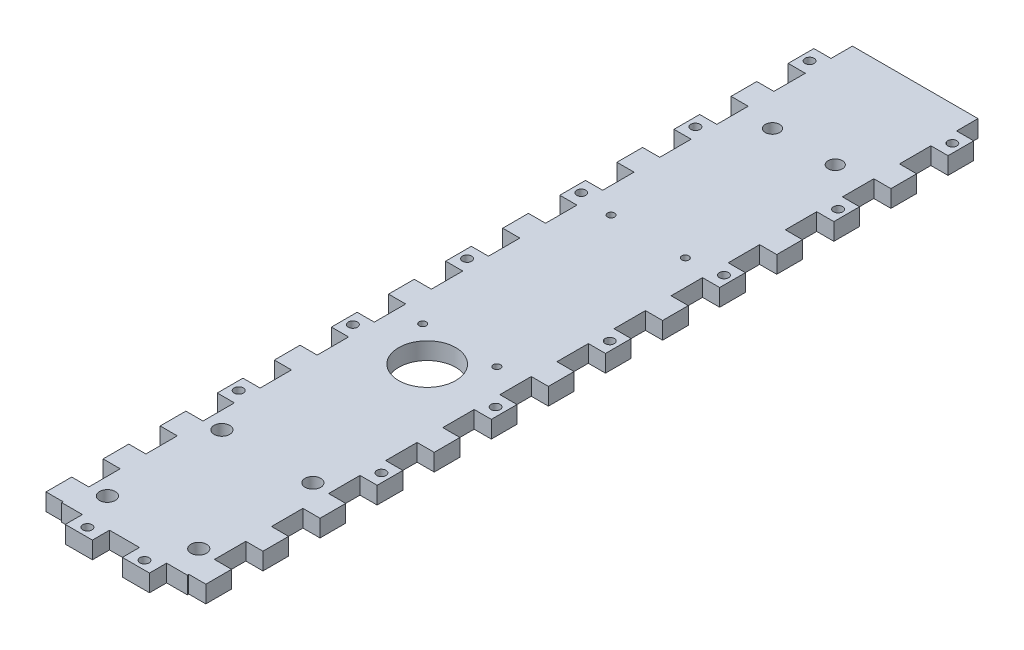
SolidWorks part; units mm, degrees
ref_plane "Plan de face" through (0, 0, 0) normal (0, 0, 1) x (1, 0, 0)
ref_plane "Plan de dessus" through (0, 0, 0) normal (0, 1, 0) x (1, 0, 0)
ref_plane "Plan de droite" through (0, 0, 0) normal (1, 0, 0) x (0, 0, -1)
sketch "Sketch1" plane through (0, 0, 0) normal (0, 0, 1) x (1, 0, 0)
  line L1 (-30.0201, 10.5217) -> (13.9799, 10.5217)
  line L2 (-30.0201, 10.5217) -> (-30.0201, 4.5217)
  line L3 (-30.0201, 4.5217) -> (13.9799, 4.5217)
  line L4 (13.9799, 10.5217) -> (13.9799, 4.5217)
  dimension "D1" = 44
  dimension "D2" = 6
extrude "Boss-Extrude1" add sketch "Sketch1" along normal blind 277
sketch "Sketch4" plane through (13.9799, 0, 0) normal (1, 0, 0) x (0, 0, -1)
  line L0 (-277, 10.5217) -> (0, 10.5217) construction
  line L1 (-276.5, 10.5217) -> (-267.5, 10.5217)
  line L2 (-276.5, 10.5217) -> (-276.5, 4.5217)
  line L3 (-276.5, 4.5217) -> (-267.5, 4.5217)
  line L4 (-267.5, 10.5217) -> (-267.5, 4.5217)
  line L5 (-277, 4.5217) -> (0, 4.5217) construction
  line L6 (-277, 4.5217) -> (-277, 10.5217) construction
  line L7 (-256.5, 10.5217) -> (-256.5, 4.5217)
  line L8 (-256.5, 10.5217) -> (-247.5, 10.5217)
  line L9 (-247.5, 10.5217) -> (-247.5, 4.5217)
  line L10 (-256.5, 4.5217) -> (-247.5, 4.5217)
  line L11 (-236.5, 10.5217) -> (-236.5, 4.5217)
  line L12 (-236.5, 10.5217) -> (-227.5, 10.5217)
  line L13 (-227.5, 10.5217) -> (-227.5, 4.5217)
  line L14 (-236.5, 4.5217) -> (-227.5, 4.5217)
  line L15 (-216.5, 10.5217) -> (-216.5, 4.5217)
  line L16 (-216.5, 10.5217) -> (-207.5, 10.5217)
  line L17 (-207.5, 10.5217) -> (-207.5, 4.5217)
  line L18 (-216.5, 4.5217) -> (-207.5, 4.5217)
  line L19 (-196.5, 10.5217) -> (-196.5, 4.5217)
  line L20 (-196.5, 10.5217) -> (-187.5, 10.5217)
  line L21 (-187.5, 10.5217) -> (-187.5, 4.5217)
  line L22 (-196.5, 4.5217) -> (-187.5, 4.5217)
  line L23 (-176.5, 10.5217) -> (-176.5, 4.5217)
  line L24 (-176.5, 10.5217) -> (-167.5, 10.5217)
  line L25 (-167.5, 10.5217) -> (-167.5, 4.5217)
  line L26 (-176.5, 4.5217) -> (-167.5, 4.5217)
  line L27 (-156.5, 10.5217) -> (-156.5, 4.5217)
  line L28 (-156.5, 10.5217) -> (-147.5, 10.5217)
  line L29 (-147.5, 10.5217) -> (-147.5, 4.5217)
  line L30 (-156.5, 4.5217) -> (-147.5, 4.5217)
  line L31 (-136.5, 10.5217) -> (-136.5, 4.5217)
  line L32 (-136.5, 10.5217) -> (-127.5, 10.5217)
  line L33 (-127.5, 10.5217) -> (-127.5, 4.5217)
  line L34 (-136.5, 4.5217) -> (-127.5, 4.5217)
  line L35 (-116.5, 10.5217) -> (-116.5, 4.5217)
  line L36 (-116.5, 10.5217) -> (-107.5, 10.5217)
  line L37 (-107.5, 10.5217) -> (-107.5, 4.5217)
  line L38 (-116.5, 4.5217) -> (-107.5, 4.5217)
  line L39 (-96.5, 10.5217) -> (-96.5, 4.5217)
  line L40 (-96.5, 10.5217) -> (-87.5, 10.5217)
  line L41 (-87.5, 10.5217) -> (-87.5, 4.5217)
  line L42 (-96.5, 4.5217) -> (-87.5, 4.5217)
  line L43 (-76.5, 10.5217) -> (-76.5, 4.5217)
  line L44 (-76.5, 10.5217) -> (-67.5, 10.5217)
  line L45 (-67.5, 10.5217) -> (-67.5, 4.5217)
  line L46 (-76.5, 4.5217) -> (-67.5, 4.5217)
  line L47 (-56.5, 10.5217) -> (-56.5, 4.5217)
  line L48 (-56.5, 10.5217) -> (-47.5, 10.5217)
  line L49 (-47.5, 10.5217) -> (-47.5, 4.5217)
  line L50 (-56.5, 4.5217) -> (-47.5, 4.5217)
  line L51 (-36.5, 10.5217) -> (-36.5, 4.5217)
  line L52 (-36.5, 10.5217) -> (-27.5, 10.5217)
  line L53 (-27.5, 10.5217) -> (-27.5, 4.5217)
  line L54 (-36.5, 4.5217) -> (-27.5, 4.5217)
  line L55 (-16.5, 10.5217) -> (-16.5, 4.5217)
  line L56 (-16.5, 10.5217) -> (-7.5, 10.5217)
  line L57 (-7.5, 10.5217) -> (-7.5, 4.5217)
  line L58 (-16.5, 4.5217) -> (-7.5, 4.5217)
  dimension "D1" = 0.5
  dimension "D2" = 9
  dimension "D3" = 14
extrude "Boss-Extrude2" add sketch "Sketch4" along normal blind 6
sketch "Sketch5" plane through (-30.0201, 0, 0) normal (-1, 0, 0) x (0, 0, 1)
  line L0 (277, 4.5217) -> (0, 4.5217) construction
  line L1 (276.5, 4.5217) -> (267.5, 4.5217)
  line L2 (276.5, 4.5217) -> (276.5, 10.5217)
  line L3 (276.5, 10.5217) -> (267.5, 10.5217)
  line L4 (267.5, 4.5217) -> (267.5, 10.5217)
  line L5 (277, 10.5217) -> (0, 10.5217) construction
  line L6 (277, 10.5217) -> (277, 4.5217) construction
  line L7 (256.5, 4.5217) -> (256.5, 10.5217)
  line L8 (256.5, 4.5217) -> (247.5, 4.5217)
  line L9 (247.5, 4.5217) -> (247.5, 10.5217)
  line L10 (256.5, 10.5217) -> (247.5, 10.5217)
  line L11 (236.5, 4.5217) -> (236.5, 10.5217)
  line L12 (236.5, 4.5217) -> (227.5, 4.5217)
  line L13 (227.5, 4.5217) -> (227.5, 10.5217)
  line L14 (236.5, 10.5217) -> (227.5, 10.5217)
  line L15 (216.5, 4.5217) -> (216.5, 10.5217)
  line L16 (216.5, 4.5217) -> (207.5, 4.5217)
  line L17 (207.5, 4.5217) -> (207.5, 10.5217)
  line L18 (216.5, 10.5217) -> (207.5, 10.5217)
  line L19 (196.5, 4.5217) -> (196.5, 10.5217)
  line L20 (196.5, 4.5217) -> (187.5, 4.5217)
  line L21 (187.5, 4.5217) -> (187.5, 10.5217)
  line L22 (196.5, 10.5217) -> (187.5, 10.5217)
  line L23 (176.5, 4.5217) -> (176.5, 10.5217)
  line L24 (176.5, 4.5217) -> (167.5, 4.5217)
  line L25 (167.5, 4.5217) -> (167.5, 10.5217)
  line L26 (176.5, 10.5217) -> (167.5, 10.5217)
  line L27 (156.5, 4.5217) -> (156.5, 10.5217)
  line L28 (156.5, 4.5217) -> (147.5, 4.5217)
  line L29 (147.5, 4.5217) -> (147.5, 10.5217)
  line L30 (156.5, 10.5217) -> (147.5, 10.5217)
  line L31 (136.5, 4.5217) -> (136.5, 10.5217)
  line L32 (136.5, 4.5217) -> (127.5, 4.5217)
  line L33 (127.5, 4.5217) -> (127.5, 10.5217)
  line L34 (136.5, 10.5217) -> (127.5, 10.5217)
  line L35 (116.5, 4.5217) -> (116.5, 10.5217)
  line L36 (116.5, 4.5217) -> (107.5, 4.5217)
  line L37 (107.5, 4.5217) -> (107.5, 10.5217)
  line L38 (116.5, 10.5217) -> (107.5, 10.5217)
  line L39 (96.5, 4.5217) -> (96.5, 10.5217)
  line L40 (96.5, 4.5217) -> (87.5, 4.5217)
  line L41 (87.5, 4.5217) -> (87.5, 10.5217)
  line L42 (96.5, 10.5217) -> (87.5, 10.5217)
  line L43 (76.5, 4.5217) -> (76.5, 10.5217)
  line L44 (76.5, 4.5217) -> (67.5, 4.5217)
  line L45 (67.5, 4.5217) -> (67.5, 10.5217)
  line L46 (76.5, 10.5217) -> (67.5, 10.5217)
  line L47 (56.5, 4.5217) -> (56.5, 10.5217)
  line L48 (56.5, 4.5217) -> (47.5, 4.5217)
  line L49 (47.5, 4.5217) -> (47.5, 10.5217)
  line L50 (56.5, 10.5217) -> (47.5, 10.5217)
  line L51 (36.5, 4.5217) -> (36.5, 10.5217)
  line L52 (36.5, 4.5217) -> (27.5, 4.5217)
  line L53 (27.5, 4.5217) -> (27.5, 10.5217)
  line L54 (36.5, 10.5217) -> (27.5, 10.5217)
  line L55 (16.5, 4.5217) -> (16.5, 10.5217)
  line L56 (16.5, 4.5217) -> (7.5, 4.5217)
  line L57 (7.5, 4.5217) -> (7.5, 10.5217)
  line L58 (16.5, 10.5217) -> (7.5, 10.5217)
  dimension "D1" = 0.5
  dimension "D2" = 9
  dimension "D3" = 14
extrude "Boss-Extrude3" add sketch "Sketch5" along normal blind 6
sketch "Sketch6" plane through (0, 0, 277) normal (0, 0, 1) x (1, 0, 0)
  line L0 (13.9799, 10.5217) -> (-30.0201, 10.5217) construction
  line L1 (-22.7701, 10.5217) -> (-13.2701, 10.5217)
  line L2 (-22.7701, 10.5217) -> (-22.7701, 4.5217)
  line L3 (-22.7701, 4.5217) -> (-13.2701, 4.5217)
  line L4 (-13.2701, 10.5217) -> (-13.2701, 4.5217)
  line L5 (-30.0201, 4.5217) -> (13.9799, 4.5217) construction
  line L6 (-30.0201, 4.5217) -> (-30.0201, 10.5217) construction
  line L7 (-2.7701, 10.5217) -> (-2.7701, 4.5217)
  line L8 (-2.7701, 10.5217) -> (6.7299, 10.5217)
  line L9 (6.7299, 10.5217) -> (6.7299, 4.5217)
  line L10 (-2.7701, 4.5217) -> (6.7299, 4.5217)
  dimension "D1" = 7.25
  dimension "D2" = 9.5
  dimension "D3" = 2
extrude "Boss-Extrude4" add sketch "Sketch6" along normal blind 6
sketch "Sketch7" plane through (0, 4.5217, 0) normal (0, -1, 0) x (1, 0, 0)
  line L0 (-8.0201, 277) -> (-8.0201, 0) construction
  line L2 (-30.0201, 0) -> (13.9799, 0) construction
  line L3 (19.9799, 276.5) -> (13.9799, 276.5) construction
  line L7 (19.9799, 256.5) -> (19.9799, 247.5) construction
  circle A0 centre (16.9799, 252) radius 1.6
  circle A1 centre (-33.0201, 252) radius 1.6
  circle A2 centre (-33.0201, 212) radius 1.6
  circle A3 centre (16.9799, 212) radius 1.6
  circle A4 centre (-33.0201, 172) radius 1.6
  circle A5 centre (16.9799, 172) radius 1.6
  circle A6 centre (-33.0201, 132) radius 1.6
  circle A7 centre (16.9799, 132) radius 1.6
  circle A8 centre (-33.0201, 92) radius 1.6
  circle A9 centre (16.9799, 92) radius 1.6
  circle A10 centre (-33.0201, 52) radius 1.6
  circle A11 centre (16.9799, 52) radius 1.6
  circle A12 centre (-33.0201, 12) radius 1.6
  circle A13 centre (16.9799, 12) radius 1.6
  point P6 (16.9799, 276.5)
  point P43 (19.9799, 252)
  dimension "D1" = 7
  dimension "D3" = 3.2
extrude "Cut-Extrude1" cut sketch "Sketch7" against normal through all
sketch "Sketch8" plane through (0, 4.5217, 0) normal (0, -1, 0) x (1, 0, 0)
  line L0 (-8.0201, 0) -> (-8.0201, 54.5316) construction
  line L1 (-30.0201, 0) -> (13.9799, 0) construction
  circle A0 centre (-19.0201, 39) radius 2.5
  circle A1 centre (2.9799, 39) radius 2.5
  dimension "D1" = 5
  dimension "D2" = 11
  dimension "D3" = 39
extrude "Cut-Extrude2" cut sketch "Sketch8" against normal blind 12
sketch "Sketch9" plane through (0, 4.5217, 0) normal (0, -1, 0) x (-1, 0, 0)
  line L2 (-6.7299, -283) -> (-6.7299, -277) construction
  line L3 (2.7701, -283) -> (-6.7299, -283) construction
  line L4 (22.7701, -283) -> (13.2701, -283) construction
  line L5 (13.2701, -283) -> (13.2701, -277) construction
  circle A0 centre (18.0201, -280) radius 1.6
  circle A1 centre (-1.9799, -280) radius 1.6
  point P2 (-6.7299, -280)
  point P5 (-1.9799, -283)
  point P12 (18.0201, -283)
  point P15 (13.2701, -280)
  dimension "D1" = 3.2
  dimension "D2" = 3.2
extrude "Cut-Extrude3" cut sketch "Sketch9" against normal blind 12
sketch "Sketch11" plane through (0, 4.5217, 0) normal (0, -1, 0) x (1, 0, 0)
  line L0 (6.7299, 277) -> (13.9799, 277) construction
  line L1 (-13.2701, 277) -> (-2.7701, 277) construction
  circle A0 centre (-24.0199, 226.8873) radius 2.75
  circle A1 centre (7.9799, 227) radius 2.75
  circle A2 centre (7.9799, 267) radius 2.75
  circle A3 centre (-24.0201, 267) radius 2.75
  point P12 (-8.0201, 277)
  dimension "D1" = 5.5
  dimension "D2" = 5.5
  dimension "D3" = 5.5
  dimension "D4" = 5.5
  dimension "D5" = 32
  dimension "D6" = 32
  dimension "D7" = 16
  dimension "D9" = 10
  dimension "D10" = 40
extrude "Cut-Extrude4" cut sketch "Sketch11" against normal through all both and the other way through all
extrude "Boss-Extrude5" add sketch "Sketch7<2>" against normal through all separate body contours A0 | A1 region at (16.9799, 4.5217, 252)
sketch "Sketch7<2>" plane through (0, 4.5217, 0) normal (0, -1, 0) x (1, 0, 0) same geometry as "Sketch7"
combine bodies "Combine1" operation type add bodies to combine 109 113 112
sketch "Sketch12" plane through (0, 10.5217, 0) normal (0, 1, 0) x (1, 0, 0)
  line L1 (-30.0201, -167.5) -> (-30.0201, -156.5) construction
  circle A0 centre (4.9799, -159.5332) radius 1.25
  circle A1 centre (-21.0201, -159.5332) radius 1.25
  circle A2 centre (-21.0201, -93.5332) radius 1.25
  circle A3 centre (4.9799, -93.5332) radius 1.25
  circle A4 centre (-8.0201, -170.9566) radius 10
  dimension "D1" = 26
  dimension "D5" = 20
  dimension "D2" = 66
  dimension "D3" = 26
  dimension "D4" = 9
  dimension "D6" = 13
extrude "Cut-Extrude5" cut sketch "Sketch12" against normal through all
